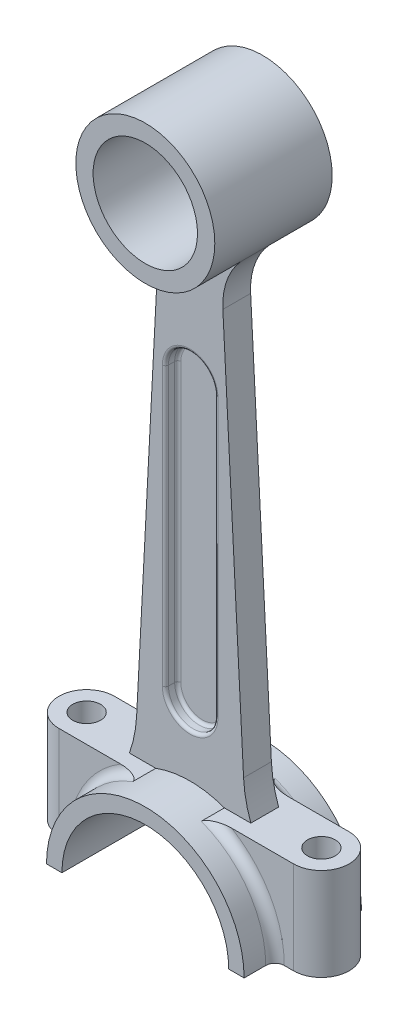
SolidWorks part; units mm, degrees
ref_plane "Front Plane" through (0, 0, 0) normal (0, 0, 1) x (1, 0, 0)
ref_plane "Top Plane" through (0, 0, 0) normal (0, 1, 0) x (1, 0, 0)
ref_plane "Right Plane" through (0, 0, 0) normal (1, 0, 0) x (0, 0, -1)
sketch "Sketch1" plane through (0, 0, 0) normal (0, 0, 1) x (1, 0, 0)
  line L0 (0, 2.9731) -> (0, -198.2269) construction
  line L1 (-10, -17.1826) -> (-18.106, -171.8539)
  line L2 (10, -17.1826) -> (18.106, -171.8539)
  line L3 (-31.9901, -198.2269) -> (-27, -198.2269)
  line L4 (27, -198.2269) -> (31.9901, -198.2269)
  circle A0 centre (0, 2.9731) radius 22.5
  circle A1 centre (0, 2.9731) radius 16.9
  arc A2 (31.9901, -198.2269) -> (-31.9901, -198.2269) centre (0, -198.2269) ccw
  arc A3 (27, -198.2269) -> (-27, -198.2269) centre (0, -198.2269) ccw
  dimension "D1" = 45
  dimension "D2" = 201.2
  dimension "D3" = 20
  dimension "D4" = 6
  dimension "D5" = 6
extrude "Boss-Extrude3" add sketch "Sketch1" along normal mid plane 38 contours A1 A0 | A2 A3 | L0 A2 L3 A3 region at (-4.9903, -18.3134, 0) region at (9.3446, -168.1055, 0) region at (-0.4524, -168.7319, 0)
extrude "Boss-Extrude5" add sketch "Sketch1<8>" along normal mid plane 9 contours A0 L0 A2 L2 | L0 A0 L1 A2 region at (7.2588, -100.3498, 0) region at (-7.2588, -100.3498, 0)
sketch "Sketch1<8>" plane through (0, 0, 0) normal (0, 0, 1) x (1, 0, 0) same geometry as "Sketch1"
sketch "Sketch3" plane through (0, 0, 4.5) normal (0, 0, 1) x (1, 0, 0)
  line L0 (0, 0) -> (0, -198.2269) construction
  line L1 (0, -54.1135) -> (0, -144.1135) construction
  line L2 (8, -54.1135) -> (8, -144.1135)
  line L3 (-8, -54.1135) -> (-8, -144.1135)
  arc A0 (8, -54.1135) -> (-8, -54.1135) centre (0, -54.1135) ccw
  arc A1 (-8, -144.1135) -> (8, -144.1135) centre (0, -144.1135) ccw
  point P6 (0, -99.1135)
  dimension "D2" = 8
  dimension "D1" = 90
extrude "Cut-Extrude1" cut sketch "Sketch3" against normal blind 4
mirror "Mirror1" about plane through (0, 0, 0) normal (0, 0, 1) of "Cut-Extrude1"
fillet "Fillet1" radius 1 16 edges at (-8, -99.1135, -4.5) (0, -46.1135, -4.5) (8, -99.1135, -4.5) (0, -46.1135, 4.5) (8, -99.1135, 4.5) (0, -152.1135, 4.5) (0, -152.1135, -4.5) (-8, -99.1135, -0.5) (0, -152.1135, -0.5) (8, -99.1135, -0.5) (0, -46.1135, -0.5) (-8, -99.1135, 4.5) (8, -99.1135, 0.5) (0, -152.1135, 0.5) (-8, -99.1135, 0.5) (0, -46.1135, 0.5)
ref_plane "Plane1" through (0, -168.2269, 0) normal (0, -1, 0) x (-1, 0, 0)
fillet "Fillet2" radius 40 1 edges at (18.106, -171.8539, 0)
fillet "Fillet3" radius 40 1 edges at (-18.106, -171.8539, 0)
fillet "Fillet4" radius 22.5 2 edges at (-10, -17.1826, 0) (10, -17.1826, 0)
sketch "Sketch4" plane through (0, -168.2269, 0) normal (0, -1, 0) x (-1, 0, 0)
  line L0 (38, 0) -> (-38, 0) construction
  line L1 (38, -9) -> (-38, -9)
  line L2 (38, 9) -> (-38, 9)
  arc A0 (38, -9) -> (38, 9) centre (38, 0) ccw
  arc A1 (-38, 9) -> (-38, -9) centre (-38, 0) ccw
  point P2 (0, 0)
  dimension "D2" = 9
  dimension "D1" = 76
extrude "Boss-Extrude7" add sketch "Sketch4" along normal up to surface (30 mm away) up to face at (29.495, -198.2269, 0)
sketch "Sketch6" plane through (0, 0, 9) normal (0, 0, 1) x (1, 0, 0)
  line L1 (-27, -198.2269) -> (27, -198.2269)
  line L2 (-27, -198.2269) -> (27, -198.2269)
  arc A1 (27, -198.2269) -> (-27, -198.2269) centre (0, -198.2269) ccw
  arc A2 (27, -198.2269) -> (-27, -198.2269) centre (0, -198.2269) ccw
  dimension "D1" = 0
extrude "Cut-Extrude3" cut sketch "Sketch6" against normal through all both and the other way through all
sketch "Sketch7" plane through (0, -168.2269, 0) normal (0, 1, 0) x (1, 0, 0)
  circle A0 centre (-38, 0) radius 4.5
  circle A1 centre (38, 0) radius 4.5
extrude "Cut-Extrude4" cut sketch "Sketch7" against normal up to surface (30 mm away) and the other way through all up to face at (33.37, -198.2269, 0)
fillet "Fillet5" radius 3 2 edges at (26.2553, -179.9506, 9) (-26.2553, -179.9506, 9)
fillet "Fillet6" radius 3 2 edges at (26.2553, -179.9506, -9) (-26.2553, -179.9506, -9)
